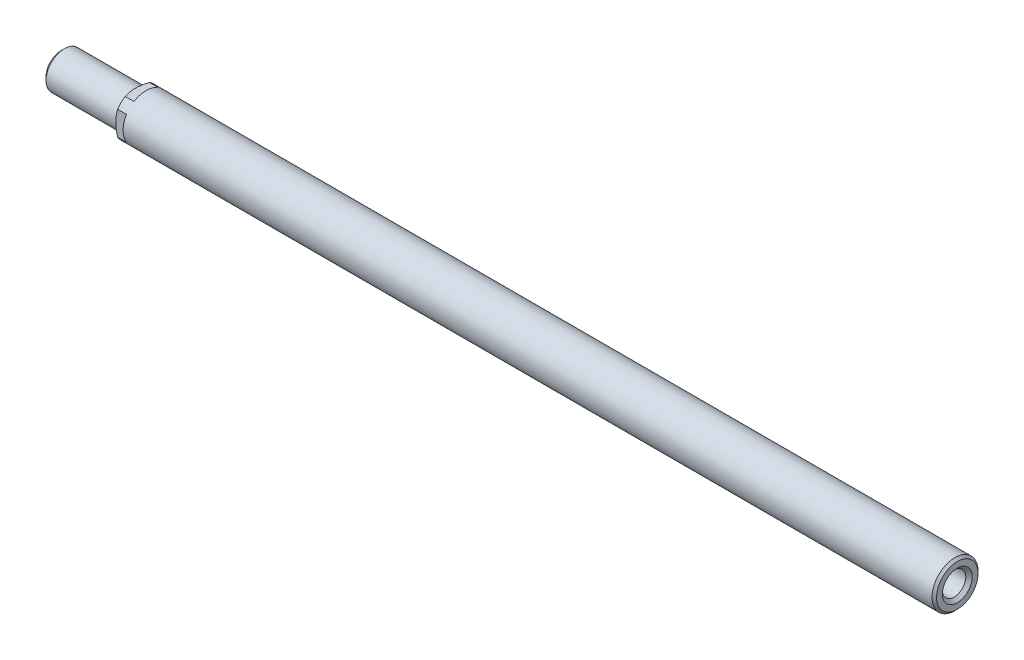
SolidWorks part; units mm, degrees
ref_plane "Płaszczyzna przednia" through (0, 0, 0) normal (0, 0, 1) x (1, 0, 0)
ref_plane "Płaszczyzna górna" through (0, 0, 0) normal (0, 1, 0) x (1, 0, 0)
ref_plane "Płaszczyzna prawa" through (0, 0, 0) normal (1, 0, 0) x (0, 0, -1)
sketch "Szkic1" plane through (0, 0, 0) normal (1, 0, 0) x (0, 0, -1)
  circle A0 centre (-94.6359, 0) radius 10
  dimension "D1" = 20
extrude "Dodanie-wyciągnięcie1" add sketch "Szkic1" against normal blind 357.5
sketch "Szkic2" plane through (-357.5, 0, 0) normal (-1, 0, 0) x (0, 0, 1)
  circle A0 centre (94.6359, 0) radius 8
  dimension "D1" = 16
extrude "Dodanie-wyciągnięcie2" add sketch "Szkic2" along normal blind 32
chamfer "Sfazowanie1" distance 1.5 angle 45 1 edges at (-389.5, 0, 102.6359)
chamfer "Sfazowanie2" distance 2 angle 30 1 edges at (-357.5, 0, 84.6359) first distance on face at (-357.5, 0, 102.6359)
ref_plane "Płaszczyzna1" through (-357.5, 0, 0) normal (-1, 0, 0) x (0, 0, 1)
sketch "Szkic3" plane through (-357.5, 0, 0) normal (-1, 0, 0) x (0, 0, 1)
  line L1 (86.1359, 8.5) -> (103.1359, 8.5)
  line L2 (86.1359, 8.5) -> (86.1359, -8.5)
  line L3 (86.1359, -8.5) -> (103.1359, -8.5)
  line L4 (103.1359, 8.5) -> (103.1359, -8.5)
  line L5 (86.1359, 8.5) -> (103.1359, -8.5) construction
  line L6 (86.1359, -8.5) -> (103.1359, 8.5) construction
  line L7 (80.3901, 13.1965) -> (108.8817, 13.1965)
  line L8 (80.3901, 13.1965) -> (80.3901, -13.1965)
  line L9 (80.3901, -13.1965) -> (108.8817, -13.1965)
  line L10 (108.8817, 13.1965) -> (108.8817, -13.1965)
  line L11 (80.3901, 13.1965) -> (108.8817, -13.1965) construction
  line L12 (80.3901, -13.1965) -> (108.8817, 13.1965) construction
  point P0 (94.6359, 0)
  point P5 (94.6359, 0)
  dimension "D1" = 17
  dimension "D2" = 17
extrude "Wytnij-wyciągnięcie1" cut sketch "Szkic3" against normal blind 5
chamfer "Sfazowanie3" distance 1 angle 45 1 edges at (0, 0, 84.6359)
sketch "Szkic4" plane through (0, 0, 0) normal (1, 0, 0) x (0, 0, -1)
  point P0 (-94.6359, 0)
hole_wizard "Otwór gwintowany M121" positions "Szkic5" profile "Szkic6" tap size "M12" standard "ISO"
sketch "Szkic5" plane through (0, 0, 0) normal (1, 0, 0) x (0, 0, -1)
  point P0 (-94.6359, 0)
sketch "Szkic6" plane through (0, 0, 94.6359) normal (0, 1, 0) x (0, 0, -1)
  line L0 (0, 0) -> (0, 21.0644)
  line L1 (0, 21.0644) -> (5.1, 18)
  line L2 (5.1, 18) -> (5.1, 1.4)
  line L3 (5.1, 1.4) -> (6.5, 0)
  line L5 (6.5, 0) -> (0, 0)
  line L6 (-5.1, 1.4) -> (-6.5, 0) construction
  line L10 (0, 21.0644) -> (-5.1, 18) construction
  line L11 (0, -6.35) -> (0, 107.95) construction
  dimension "Średnica wiertła gwintu" = 10.2
  dimension "Głębokość otworu gwintowanego" = 18
  dimension "Średnica zewnętrznego pogłębienia stożkowego" = 13
  dimension "Kąt zewnętrznego pogłębienia stożkowego" = 90
  dimension "Kąt wiertła" = 118
cosmetic thread "Gwint otworu1" parameters "D1"=16, "D2"=12
